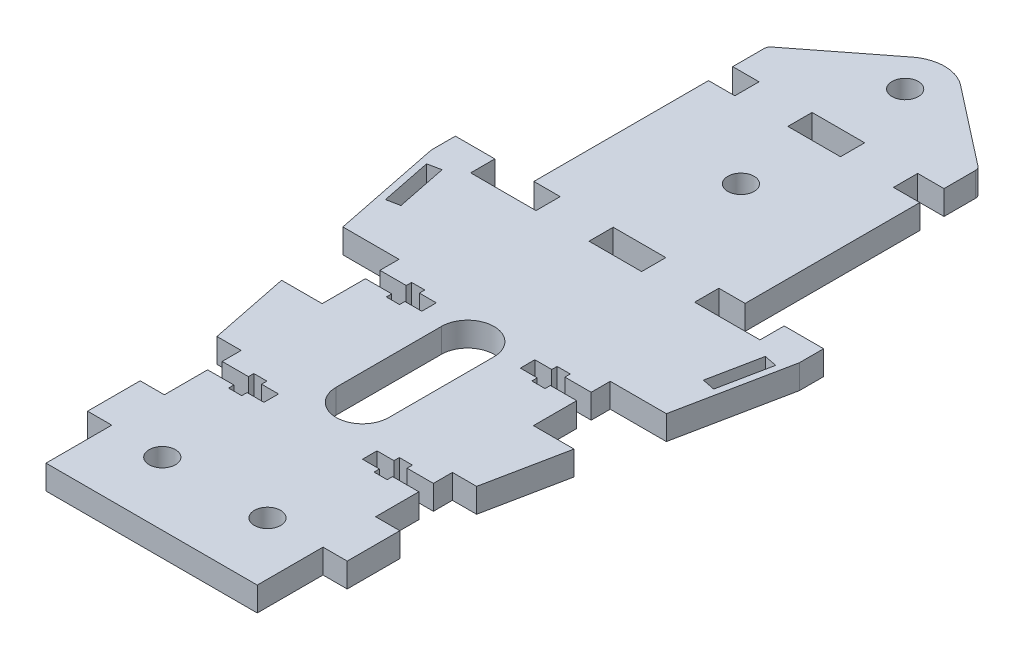
SolidWorks part; units mm, degrees
ref_plane "Front Plane" through (0, 0, 0) normal (0, 0, 1) x (1, 0, 0)
ref_plane "Top Plane" through (0, 0, 0) normal (0, 1, 0) x (1, 0, 0)
ref_plane "Right Plane" through (0, 0, 0) normal (1, 0, 0) x (0, 0, -1)
sketch "Sketch1" plane through (0, 0, 0) normal (0, 1, 0) x (1, 0, 0)
  line L0 (0, 96.7012) -> (0, 26.7242) construction
  line L1 (31.75, 26.7242) -> (25.5, 26.7242)
  line L2 (25.5, -85.217) -> (25.5, -69.342)
  line L3 (-25.5, -69.9464) -> (25.5, -69.9464) construction
  line L4 (0, 26.7242) -> (0, -69.9464) construction
  line L5 (25.5, -88.9) -> (-25.5, 88.9) construction
  line L6 (25.5, 88.9) -> (-25.5, -88.9) construction
  line L7 (-25.5, 77.6512) -> (25.5, 77.6512) construction
  line L8 (-25.5, -85.217) -> (-25.5, -69.342)
  line L9 (-25.5, 88.9) -> (-5.8561, 104.2134)
  line L10 (-25.5, 80.5722) -> (-25.5, 88.9)
  line L11 (5.8561, 104.2134) -> (25.5, 88.9)
  line L12 (-19.15, 74.7302) -> (-25.5, 74.7302)
  line L13 (-19.15, 74.7302) -> (-19.15, 80.5722)
  line L14 (-19.15, 80.5722) -> (-25.5, 80.5722)
  line L15 (19.15, 74.7302) -> (25.5, 74.7302)
  line L16 (-19.15, 74.7302) -> (-25.5, 80.5722) construction
  line L17 (-19.15, 80.5722) -> (-25.5, 74.7302) construction
  line L18 (6.35, 74.7302) -> (-6.35, 74.7302)
  line L19 (6.35, 74.7302) -> (6.35, 80.5722)
  line L20 (6.35, 80.5722) -> (-6.35, 80.5722)
  line L21 (-6.35, 74.7302) -> (-6.35, 80.5722)
  line L22 (6.35, 74.7302) -> (-6.35, 80.5722) construction
  line L23 (6.35, 80.5722) -> (-6.35, 74.7302) construction
  line L24 (19.15, 74.7302) -> (19.15, 80.5722)
  line L25 (19.15, 80.5722) -> (25.5, 80.5722)
  line L26 (25.5, 80.5722) -> (25.5, 88.9)
  line L27 (0, -69.9464) -> (0, -88.9) construction
  line L28 (0, -69.9464) -> (0, 26.7242) construction
  line L29 (0, -8.9111) -> (0, -34.3111) construction
  line L30 (6.35, -8.9111) -> (6.35, -34.3111)
  line L31 (-6.35, -8.9111) -> (-6.35, -34.3111)
  line L32 (-25.5, 53.6482) -> (25.5, 53.6482) construction
  line L33 (19.15, 32.5662) -> (25.5, 32.5662)
  line L34 (19.15, 32.5662) -> (19.15, 26.7242)
  line L35 (19.15, 26.7242) -> (25.5, 26.7242)
  line L36 (6.35, 32.5662) -> (6.35, 26.7242)
  line L37 (6.35, 32.5662) -> (-6.35, 32.5662)
  line L38 (6.35, 26.7242) -> (-6.35, 26.7242)
  line L39 (-6.35, 32.5662) -> (-6.35, 26.7242)
  line L40 (-19.15, 26.7242) -> (-25.5, 26.7242)
  line L41 (-19.15, 32.5662) -> (-19.15, 26.7242)
  line L42 (-19.15, 32.5662) -> (-25.5, 32.5662)
  line L43 (-25.5, 32.5662) -> (-25.5, 74.7302)
  line L44 (25.5, 32.5662) -> (25.5, 74.7302)
  line L45 (-44.45, 32.5662) -> (-34.925, 32.5662)
  line L46 (-31.75, 26.7242) -> (-25.5, 26.7242)
  line L47 (-44.45, 32.5662) -> (-44.45, 26.7242)
  line L48 (-25.5, -38.1) -> (-31.342, -38.1)
  line L49 (-34.925, 32.5662) -> (-34.925, 26.7242)
  line L50 (-44.45, 32.5662) -> (-31.75, 26.7242) construction
  line L51 (-44.45, 26.7242) -> (-31.75, 32.5662) construction
  line L52 (-31.342, -38.1) -> (-35.2968, -18.542)
  line L53 (-31.342, 0) -> (-39.0461, 0)
  line L54 (-31.342, -69.342) -> (-25.5, -69.342)
  line L55 (-31.342, -69.342) -> (-31.342, -56.642)
  line L56 (-31.342, -56.642) -> (-25.5, -56.642)
  line L57 (-25.5, -85.217) -> (25.5, -85.217)
  line L58 (-31.342, -69.342) -> (-25.5, -56.642) construction
  line L59 (-31.342, -56.642) -> (-25.5, -69.342) construction
  line L60 (-31.342, 0) -> (-25.5, 0)
  line L61 (-39.0461, 0) -> (-44.45, 26.7242)
  line L62 (-31.342, -18.542) -> (-25.5, -18.542)
  line L63 (-25.5, 0) -> (-25.5, -18.542)
  line L64 (-31.342, 0) -> (-25.5, -18.542) construction
  line L65 (-31.342, -18.542) -> (-25.5, 0) construction
  line L66 (-31.342, -18.542) -> (-35.2968, -18.542)
  line L67 (-25.5, -56.642) -> (-25.5, -38.1)
  line L68 (31.342, 0) -> (25.5, 0)
  line L69 (31.342, -18.542) -> (25.5, -18.542)
  line L70 (25.5, -38.1) -> (31.342, -38.1)
  line L71 (31.342, -69.342) -> (25.5, -69.342)
  line L72 (31.342, -56.642) -> (25.5, -56.642)
  line L73 (44.45, 32.5662) -> (44.45, 26.7242)
  line L74 (44.45, 32.5662) -> (34.925, 32.5662)
  line L75 (31.342, -18.542) -> (35.2968, -18.542)
  line L76 (39.0461, 0) -> (44.45, 26.7242)
  line L77 (31.342, -69.342) -> (31.342, -56.642)
  line L78 (31.342, 0) -> (39.0461, 0)
  line L79 (31.342, -38.1) -> (35.2968, -18.542)
  line L80 (34.925, 32.5662) -> (34.925, 26.7242)
  line L81 (34.925, 26.7242) -> (31.75, 26.7242)
  line L83 (25.5, -18.542) -> (25.5, 0)
  line L84 (25.5, -56.642) -> (25.5, -38.1)
  line L85 (-34.925, 26.7242) -> (-31.75, 26.7242)
  circle A0 centre (0, 96.7012) radius 3.175
  circle A1 centre (0, 57.0536) radius 3.175
  arc A4 (5.8561, 104.2134) -> (-5.8561, 104.2134) centre (0, 96.7012) ccw
  circle A5 centre (-12.7, -69.9464) radius 3.175
  circle A6 centre (12.7, -69.9464) radius 3.175
  arc A7 (6.35, -8.9111) -> (-6.35, -8.9111) centre (0, -8.9111) ccw
  arc A8 (-6.35, -34.3111) -> (6.35, -34.3111) centre (0, -34.3111) ccw
  point P0 (0, 0)
  point P14 (-38.1, 29.6452)
  point P17 (-6.35, 29.6452)
  point P21 (-22.325, 77.6512)
  point P28 (0, 77.6512)
  point P45 (0, -21.6111)
  point P66 (-28.421, -62.992)
  point P72 (-28.421, -9.271)
  point P97 (28.421, -9.271)
  point P98 (28.421, -62.992)
  point P99 (38.1, 29.6452)
  dimension "D3" = 6.35
  dimension "D4" = 6.35
  dimension "D5" = 39.6476
  dimension "D6" = 12.7
  dimension "D7" = 5.842
  dimension "D8" = 38.1
  dimension "D9" = 19.05
  dimension "D10" = 19.05
  dimension "D15" = 6.35
  dimension "D17" = 6.35
  dimension "D1" = 51
  dimension "D2" = 177.8
  dimension "D11" = 5.842
  dimension "D12" = 6.35
  dimension "D13" = 12.7
  dimension "D14" = 50.8
  dimension "D16" = 12.7
  dimension "D18" = 21.082
  dimension "D19" = 5.842
  dimension "D20" = 5.842
  dimension "D21" = 12.7
  dimension "D22" = 18.542
  dimension "D23" = 5.842
  dimension "D24" = 18.542
  dimension "D25" = 38.1
  dimension "D26" = 15.875
  dimension "D27" = 9.525
  dimension "D28" = 127
extrude "Boss-Extrude1" add sketch "Sketch1" along normal blind 5.842
sketch "Sketch2" plane through (0, 5.842, 0) normal (0, 1, 0) x (1, 0, 0)
  line L0 (0, 26.7242) -> (0, -85.217) construction
  line L1 (-6.35, 26.7242) -> (6.35, 26.7242) construction
  line L2 (-25.5, -85.217) -> (25.5, -85.217) construction
  line L3 (-25.5, -6.35) -> (25.5, -6.35) construction
  line L4 (-25.5, 0) -> (-25.5, -18.542) construction
  line L5 (25.5, -18.542) -> (25.5, 0) construction
  line L6 (-25.5, -44.45) -> (25.5, -44.45) construction
  line L7 (-25.5, -38.1) -> (-25.5, -56.642) construction
  line L8 (25.5, -56.642) -> (25.5, -38.1) construction
  line L9 (-39.0461, 0) -> (-25.5, 0) construction
  line L10 (-31.342, -38.1) -> (-25.5, -38.1) construction
  line L11 (-15.975, -42.6974) -> (-15.975, -41.402)
  line L12 (-19.15, -46.2026) -> (-25.5, -46.2026)
  line L13 (-1.3648, -6.35) -> (-1.3648, -44.45) construction
  line L14 (-19.15, -42.6974) -> (-25.5, -42.6974)
  line L15 (-25.5, -46.2026) -> (-25.5, -42.6974)
  line L16 (-19.15, -46.2026) -> (-25.5, -42.6974) construction
  line L17 (-19.15, -42.6974) -> (-25.5, -46.2026) construction
  line L18 (-15.975, -47.498) -> (-19.15, -47.498)
  line L19 (-15.975, -47.498) -> (-15.975, -46.2026)
  line L20 (-15.975, -41.402) -> (-19.15, -41.402)
  line L21 (-19.15, -47.498) -> (-19.15, -46.2026)
  line L22 (-15.975, -47.498) -> (-19.15, -41.402) construction
  line L23 (-15.975, -41.402) -> (-19.15, -47.498) construction
  line L24 (-11.892, -46.2026) -> (-15.975, -46.2026)
  line L25 (-11.892, -46.2026) -> (-11.892, -42.6974)
  line L26 (-11.892, -42.6974) -> (-15.975, -42.6974)
  line L27 (-19.15, -42.6974) -> (-19.15, -41.402)
  line L28 (-11.892, -46.2026) -> (-15.975, -42.6974) construction
  line L29 (-11.892, -42.6974) -> (-15.975, -46.2026) construction
  line L30 (-1.3648, -25.4) -> (0, -25.4) construction
  line L31 (-11.892, -8.1026) -> (-15.975, -4.5974) construction
  line L32 (-11.892, -4.5974) -> (-15.975, -8.1026) construction
  line L33 (-15.975, -9.398) -> (-19.15, -3.302) construction
  line L34 (-15.975, -3.302) -> (-19.15, -9.398) construction
  line L35 (-19.15, -8.1026) -> (-25.5, -4.5974) construction
  line L36 (-19.15, -4.5974) -> (-25.5, -8.1026) construction
  line L37 (-19.15, -8.1026) -> (-19.15, -9.398)
  line L38 (-11.892, -8.1026) -> (-15.975, -8.1026)
  line L39 (-11.892, -4.5974) -> (-11.892, -8.1026)
  line L40 (-11.892, -4.5974) -> (-15.975, -4.5974)
  line L41 (-19.15, -3.302) -> (-19.15, -4.5974)
  line L42 (-15.975, -9.398) -> (-19.15, -9.398)
  line L43 (-15.975, -3.302) -> (-15.975, -4.5974)
  line L44 (-15.975, -3.302) -> (-19.15, -3.302)
  line L45 (-25.5, -4.5974) -> (-25.5, -8.1026)
  line L46 (-19.15, -8.1026) -> (-25.5, -8.1026)
  line L47 (-19.15, -4.5974) -> (-25.5, -4.5974)
  line L48 (-15.975, -8.1026) -> (-15.975, -9.398)
  line L49 (19.15, -4.5974) -> (25.5, -8.1026) construction
  line L50 (19.15, -8.1026) -> (25.5, -4.5974) construction
  line L51 (15.975, -3.302) -> (19.15, -9.398) construction
  line L52 (15.975, -9.398) -> (19.15, -3.302) construction
  line L53 (11.892, -4.5974) -> (15.975, -8.1026) construction
  line L54 (11.892, -8.1026) -> (15.975, -4.5974) construction
  line L55 (11.892, -42.6974) -> (15.975, -46.2026) construction
  line L56 (11.892, -46.2026) -> (15.975, -42.6974) construction
  line L57 (15.975, -41.402) -> (19.15, -47.498) construction
  line L58 (15.975, -47.498) -> (19.15, -41.402) construction
  line L59 (19.15, -42.6974) -> (25.5, -46.2026) construction
  line L60 (19.15, -46.2026) -> (25.5, -42.6974) construction
  line L61 (15.975, -8.1026) -> (15.975, -9.398)
  line L62 (19.15, -4.5974) -> (25.5, -4.5974)
  line L63 (19.15, -8.1026) -> (25.5, -8.1026)
  line L64 (25.5, -4.5974) -> (25.5, -8.1026)
  line L65 (15.975, -3.302) -> (19.15, -3.302)
  line L66 (15.975, -3.302) -> (15.975, -4.5974)
  line L67 (15.975, -9.398) -> (19.15, -9.398)
  line L68 (19.15, -3.302) -> (19.15, -4.5974)
  line L69 (11.892, -4.5974) -> (15.975, -4.5974)
  line L70 (11.892, -4.5974) -> (11.892, -8.1026)
  line L71 (11.892, -8.1026) -> (15.975, -8.1026)
  line L72 (19.15, -8.1026) -> (19.15, -9.398)
  line L73 (19.15, -42.6974) -> (19.15, -41.402)
  line L74 (11.892, -42.6974) -> (15.975, -42.6974)
  line L75 (11.892, -46.2026) -> (11.892, -42.6974)
  line L76 (11.892, -46.2026) -> (15.975, -46.2026)
  line L77 (19.15, -47.498) -> (19.15, -46.2026)
  line L78 (15.975, -41.402) -> (19.15, -41.402)
  line L79 (15.975, -47.498) -> (15.975, -46.2026)
  line L80 (15.975, -47.498) -> (19.15, -47.498)
  line L81 (25.5, -46.2026) -> (25.5, -42.6974)
  line L82 (19.15, -42.6974) -> (25.5, -42.6974)
  line L83 (19.15, -46.2026) -> (25.5, -46.2026)
  line L84 (15.975, -42.6974) -> (15.975, -41.402)
  point P22 (-22.325, -44.45)
  point P27 (-17.5625, -44.45)
  point P32 (-13.9335, -44.45)
  point P53 (-13.9335, -6.35)
  point P54 (-17.5625, -6.35)
  point P55 (-22.325, -6.35)
  point P80 (22.325, -6.35)
  point P81 (17.5625, -6.35)
  point P82 (13.9335, -6.35)
  point P83 (13.9335, -44.45)
  point P84 (17.5625, -44.45)
  point P85 (22.325, -44.45)
  dimension "D1" = 6.35
  dimension "D2" = 6.35
  dimension "D3" = 3.5052
  dimension "D4" = 6.35
  dimension "D5" = 6.096
  dimension "D6" = 3.175
  dimension "D7" = 4.083
extrude "Cut-Extrude1" cut sketch "Sketch2" against normal through all
fillet "Fillet1" radius 1.5875 2 edges at (25.5, 2.921, -88.9) (-25.5, 2.921, -88.9)
sketch "Sketch3" plane through (0, 5.842, 0) normal (0, 1, 0) x (1, 0, 0)
  line L0 (-44.45, 26.7242) -> (44.45, 26.7242) construction
  line L2 (-41.2107, 26.7242) -> (-28.1027, -38.1) construction
  line L3 (-35.2968, -18.542) -> (-31.342, -38.1) construction
  line L4 (0, 26.7242) -> (0, -38.1) construction
  line L5 (-42.1375, 23.2976) -> (-39.6204, 10.8495)
  line L6 (-42.1375, 23.2976) -> (-39.0255, 23.9269)
  line L7 (-39.6204, 10.8495) -> (-36.5084, 11.4788)
  line L8 (-39.0255, 23.9269) -> (-36.5084, 11.4788)
  line L9 (-42.1375, 23.2976) -> (-36.5084, 11.4788) construction
  line L10 (-39.6204, 10.8495) -> (-39.0255, 23.9269) construction
  line L11 (-32.313, -5.214) -> (-37.0004, -6.1618) construction
  line L20 (32.313, -5.214) -> (37.0004, -6.1618) construction
  line L21 (39.6204, 10.8495) -> (39.0255, 23.9269) construction
  line L22 (42.1375, 23.2976) -> (36.5084, 11.4788) construction
  line L23 (41.2107, 26.7242) -> (28.1027, -38.1) construction
  line L28 (39.0255, 23.9269) -> (36.5084, 11.4788)
  line L29 (39.6204, 10.8495) -> (36.5084, 11.4788)
  line L30 (42.1375, 23.2976) -> (39.0255, 23.9269)
  line L31 (42.1375, 23.2976) -> (39.6204, 10.8495)
  point P15 (-39.3229, 17.3882)
  point P22 (-34.6567, -5.6879)
  point P40 (34.6567, -5.6879)
  point P41 (39.3229, 17.3882)
  dimension "D1" = 3.175
  dimension "D2" = 3.175
  dimension "D3" = 12.7
  dimension "D4" = 9.525
extrude "Cut-Extrude2" cut sketch "Sketch3" against normal through all
